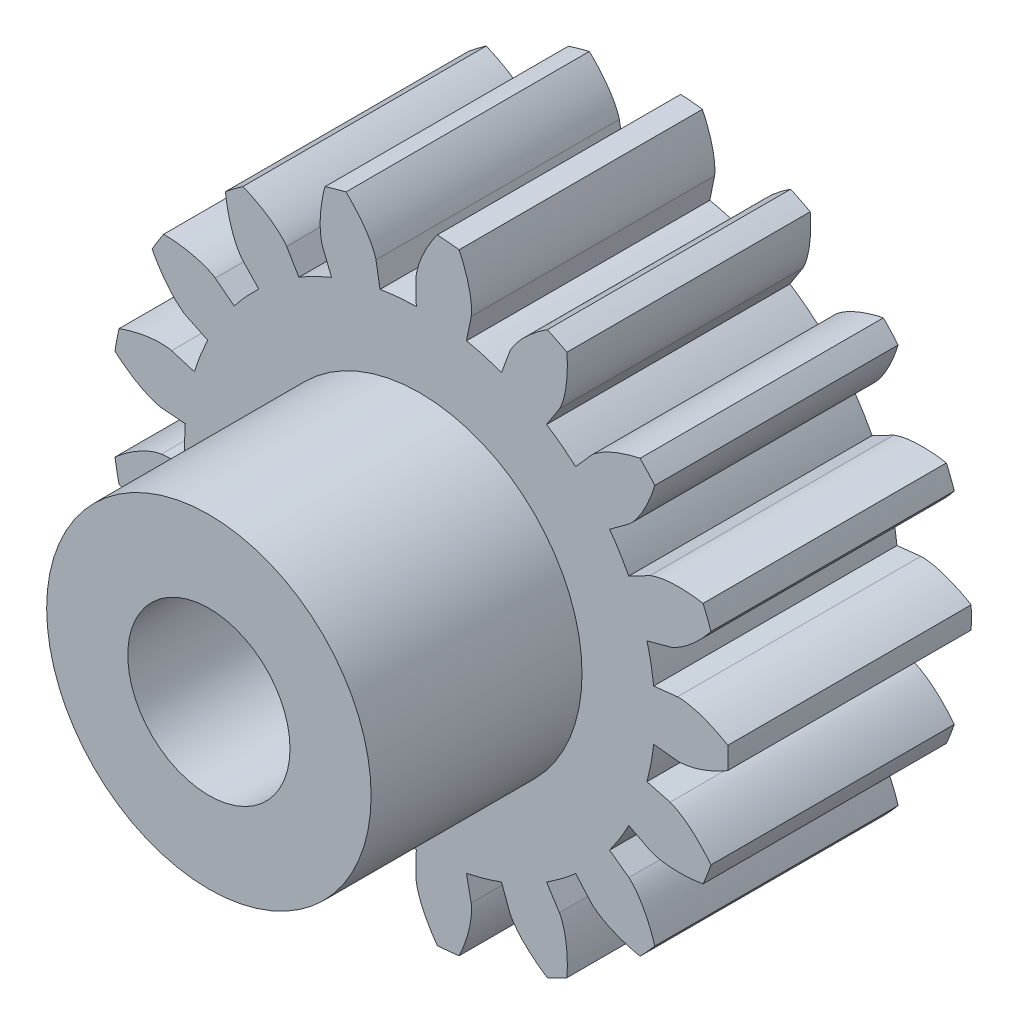
SolidWorks part; units mm, degrees
other "Kamera1"
ref_plane "Płaszczyzna przednia" through (0, 0, 0) normal (0, 0, 1) x (1, 0, 0)
ref_plane "Płaszczyzna górna" through (0, 0, 0) normal (0, 1, 0) x (1, 0, 0)
ref_plane "Płaszczyzna prawa" through (0, 0, 0) normal (1, 0, 0) x (0, 0, -1)
sketch "Szkic1" plane through (0, 0, 0) normal (0, 0, 1) x (1, 0, 0)
  circle A0 centre (0, 0) radius 9.5
extrude "Dodanie-wyciągnięcie1" add sketch "Szkic1" along normal blind 7.5
sketch "Szkic2" plane through (0, 0, 7.5) normal (0, 0, 1) x (1, 0, 0)
  circle A0 centre (0, 0) radius 5
extrude "Dodanie-wyciągnięcie2" add sketch "Szkic2" along normal blind 6.5
sketch "Szkic3" plane through (0, 0, 14) normal (0, 0, 1) x (1, 0, 0)
  circle A0 centre (0, 0) radius 2.5
extrude "Wytnij-wyciągnięcie1" cut sketch "Szkic3" against normal through all
sketch "Szkic5" plane through (0, 0, 0) normal (0, 0, -1) x (-1, 0, 0)
  line L0 (7.9634, 0.6184) -> (7.2282, 0.5613)
  line L1 (7.2282, -0.5613) -> (7.9634, -0.6184)
  line L2 (7.649, -2.3001) -> (6.9429, -2.0878)
  line L3 (6.5374, -3.1345) -> (7.2023, -3.4533)
  line L4 (6.3016, -4.9079) -> (5.7199, -4.4548)
  line L5 (4.9636, -5.2844) -> (5.4684, -5.8219)
  line L6 (4.1031, -6.8529) -> (3.7243, -6.2203)
  line L7 (2.7195, -6.7206) -> (2.9961, -7.4042)
  line L8 (1.3505, -7.8724) -> (1.2258, -7.1456)
  line L9 (0.1081, -7.2492) -> (0.119, -7.9865)
  line L10 (-1.5845, -7.8286) -> (-1.4382, -7.1059)
  line L11 (-2.518, -6.7987) -> (-2.7741, -7.4902)
  line L12 (-4.3056, -6.7276) -> (-3.9081, -6.1065)
  line L13 (-4.8039, -5.43) -> (-5.2925, -5.9823)
  line L14 (-6.4451, -4.7179) -> (-5.8501, -4.2824)
  line L15 (-6.441, -3.328) -> (-7.0962, -3.6665)
  line L16 (-7.7142, -2.0711) -> (-7.002, -1.8799)
  line L17 (-7.2083, -0.7765) -> (-7.9414, -0.8554)
  line L18 (-7.9414, 0.8554) -> (-7.2083, 0.7765)
  line L19 (-7.002, 1.8799) -> (-7.7142, 2.0711)
  line L20 (-7.0962, 3.6665) -> (-6.441, 3.328)
  line L21 (-5.8501, 4.2824) -> (-6.4451, 4.7179)
  line L22 (-5.2925, 5.9823) -> (-4.8039, 5.43)
  line L23 (-3.9081, 6.1065) -> (-4.3056, 6.7276)
  line L24 (-2.7741, 7.4902) -> (-2.518, 6.7987)
  line L25 (-1.4382, 7.1059) -> (-1.5845, 7.8286)
  line L26 (0.119, 7.9865) -> (0.1081, 7.2492)
  line L27 (1.2258, 7.1456) -> (1.3505, 7.8724)
  line L28 (2.9961, 7.4042) -> (2.7195, 6.7206)
  line L29 (3.7243, 6.2203) -> (4.1031, 6.8529)
  line L30 (5.4684, 5.8219) -> (4.9636, 5.2844)
  line L31 (5.7199, 4.4548) -> (6.3016, 4.9079)
  line L32 (7.2023, 3.4533) -> (6.5374, 3.1345)
  line L33 (6.9429, 2.0878) -> (7.649, 2.3001)
  circle A1 centre (0, 0) radius 9.5
  spline S0 degree 4 poles (7.9634, -0.6184) (7.9667, -0.6187) (7.976, -0.6197) (7.9934, -0.6223) (8.0218, -0.6274) (8.0577, -0.6353) (8.1038, -0.647) (8.1577, -0.6627) (8.2166, -0.682) (8.2801, -0.7052) (8.3429, -0.7302) (8.405, -0.757) (8.4665, -0.7852) (8.5402, -0.8212) (8.6279, -0.867) (8.7289, -0.9243) (8.8418, -0.9935) (8.9549, -1.0687) (9.0646, -1.1464) (9.1734, -1.2291) (9.2772, -1.3122) (9.3829, -1.4026) (9.4793, -1.4883) (9.5847, -1.5888) (9.669, -1.6713) (9.7774, -1.7849) (9.8406, -1.8533) (9.9135, -1.9351) (9.9453, -1.9723) (9.9649, -1.9951) knots 0 0 0 0 0 0.005377 0.015084 0.028532 0.04661 0.064855 0.092111 0.119476 0.146842 0.174209 0.201575 0.228941 0.256307 0.307035 0.361767 0.4165 0.471232 0.525964 0.580697 0.635429 0.690161 0.744894 0.799626 0.854358 0.909091 0.954545 1 1 1 1 1 construction
  spline S1 degree 4 poles (7.9634, -0.6184) (7.9667, -0.6187) (7.976, -0.6197) (7.9934, -0.6223) (8.0218, -0.6274) (8.0577, -0.6353) (8.1038, -0.647) (8.1577, -0.6627) (8.2166, -0.682) (8.2801, -0.7052) (8.3429, -0.7302) (8.405, -0.757) (8.4665, -0.7852) (8.5402, -0.8212) (8.6279, -0.867) (8.7289, -0.9243) (8.8418, -0.9935) (8.9549, -1.0687) (9.0646, -1.1464) (9.1734, -1.2291) (9.2772, -1.3122) (9.3829, -1.4026) (9.4793, -1.4883) (9.5847, -1.5888) (9.669, -1.6713) (9.7539, -1.7602) (9.7949, -1.8041) (9.8157, -1.8267) knots 0 0 0 0 0 0.005377 0.015084 0.028532 0.04661 0.064855 0.092111 0.119476 0.146842 0.174209 0.201575 0.228941 0.256307 0.307035 0.361767 0.4165 0.471232 0.525964 0.580697 0.635429 0.690161 0.744894 0.799626 0.854358 0.909091 0.909091 0.909091 0.909091 0.909091
  spline S2 degree 4 poles (7.9634, 0.6184) (7.9667, 0.6187) (7.976, 0.6197) (7.9934, 0.6223) (8.0218, 0.6274) (8.0577, 0.6353) (8.1038, 0.647) (8.1577, 0.6627) (8.2166, 0.682) (8.2801, 0.7052) (8.3429, 0.7302) (8.405, 0.757) (8.4665, 0.7852) (8.5402, 0.8212) (8.6279, 0.867) (8.7289, 0.9243) (8.8418, 0.9935) (8.9549, 1.0687) (9.0646, 1.1464) (9.1734, 1.2291) (9.2772, 1.3122) (9.3829, 1.4026) (9.4793, 1.4883) (9.5847, 1.5888) (9.669, 1.6713) (9.7774, 1.7849) (9.8406, 1.8533) (9.9135, 1.9351) (9.9453, 1.9723) (9.9649, 1.9951) knots 0 0 0 0 0 0.005377 0.015084 0.028532 0.04661 0.064855 0.092111 0.119476 0.146842 0.174209 0.201575 0.228941 0.256307 0.307035 0.361767 0.4165 0.471232 0.525964 0.580697 0.635429 0.690161 0.744894 0.799626 0.854358 0.909091 0.954545 1 1 1 1 1 construction
  spline S3 degree 4 poles (7.9634, 0.6184) (7.9667, 0.6187) (7.976, 0.6197) (7.9934, 0.6223) (8.0218, 0.6274) (8.0577, 0.6353) (8.1038, 0.647) (8.1577, 0.6627) (8.2166, 0.682) (8.2801, 0.7052) (8.3429, 0.7302) (8.405, 0.757) (8.4665, 0.7852) (8.5402, 0.8212) (8.6279, 0.867) (8.7289, 0.9243) (8.8418, 0.9935) (8.9549, 1.0687) (9.0646, 1.1464) (9.1734, 1.2291) (9.2772, 1.3122) (9.3829, 1.4026) (9.4793, 1.4883) (9.5847, 1.5888) (9.669, 1.6713) (9.7539, 1.7602) (9.7949, 1.8041) (9.8157, 1.8267) knots 0 0 0 0 0 0.005377 0.015084 0.028532 0.04661 0.064855 0.092111 0.119476 0.146842 0.174209 0.201575 0.228941 0.256307 0.307035 0.361767 0.4165 0.471232 0.525964 0.580697 0.635429 0.690161 0.744894 0.799626 0.854358 0.909091 0.909091 0.909091 0.909091 0.909091
  spline S4 degree 2 poles (7.2282, 0.5613) (7.2716, -0.0034) (7.2282, -0.5613) knots 0 0 0 0.499734 0.499734 0.499734
  spline S5 degree 2 poles (6.9429, -2.0878) (6.7793, -2.6299) (6.5374, -3.1345) knots 0 0 0 0.499734 0.499734 0.499734
  spline S6 degree 4 poles (7.2023, -3.4533) (7.2053, -3.4548) (7.2135, -3.4591) (7.2288, -3.4678) (7.2534, -3.4829) (7.284, -3.5032) (7.3228, -3.5307) (7.3675, -3.5649) (7.4154, -3.6041) (7.4662, -3.6487) (7.5157, -3.6947) (7.564, -3.7421) (7.6111, -3.7906) (7.6669, -3.8509) (7.732, -3.9252) (7.8056, -4.0151) (7.8858, -4.1205) (7.9641, -4.2314) (8.0383, -4.3435) (8.1099, -4.4599) (8.1767, -4.5749) (8.2426, -4.6974) (8.3015, -4.8121) (8.3635, -4.9439) (8.4124, -5.0513) (8.4724, -5.1963) (8.5066, -5.283) (8.545, -5.3856) (8.5612, -5.4317) (8.5713, -5.4601) knots 0 0 0 0 0 0.005377 0.015084 0.028532 0.04661 0.064855 0.092111 0.119476 0.146842 0.174209 0.201575 0.228941 0.256307 0.307035 0.361767 0.4165 0.471232 0.525964 0.580697 0.635429 0.690161 0.744894 0.799626 0.854358 0.909091 0.954545 1 1 1 1 1 construction
  spline S7 degree 4 poles (7.2023, -3.4533) (7.2053, -3.4548) (7.2135, -3.4591) (7.2288, -3.4678) (7.2534, -3.4829) (7.284, -3.5032) (7.3228, -3.5307) (7.3675, -3.5649) (7.4154, -3.6041) (7.4662, -3.6487) (7.5157, -3.6947) (7.564, -3.7421) (7.6111, -3.7906) (7.6669, -3.8509) (7.732, -3.9252) (7.8056, -4.0151) (7.8858, -4.1205) (7.9641, -4.2314) (8.0383, -4.3435) (8.1099, -4.4599) (8.1767, -4.5749) (8.2426, -4.6974) (8.3015, -4.8121) (8.3635, -4.9439) (8.4124, -5.0513) (8.4594, -5.1649) (8.4818, -5.2206) (8.493, -5.2492) knots 0 0 0 0 0 0.005377 0.015084 0.028532 0.04661 0.064855 0.092111 0.119476 0.146842 0.174209 0.201575 0.228941 0.256307 0.307035 0.361767 0.4165 0.471232 0.525964 0.580697 0.635429 0.690161 0.744894 0.799626 0.854358 0.909091 0.909091 0.909091 0.909091 0.909091
  spline S8 degree 4 poles (7.649, -2.3001) (7.6522, -2.301) (7.6612, -2.3034) (7.6784, -2.3073) (7.7067, -2.3127) (7.743, -2.3184) (7.7903, -2.3241) (7.8463, -2.329) (7.9081, -2.3322) (7.9757, -2.3335) (8.0433, -2.3329) (8.1109, -2.3304) (8.1784, -2.3263) (8.2602, -2.3193) (8.3584, -2.3083) (8.4733, -2.2914) (8.6036, -2.2676) (8.7363, -2.2383) (8.8666, -2.2055) (8.9979, -2.1677) (9.1247, -2.1278) (9.2559, -2.0816) (9.3768, -2.0365) (9.5114, -1.9809) (9.6198, -1.9344) (9.7619, -1.8677) (9.8456, -1.8266) (9.9431, -1.7767) (9.9862, -1.7536) (10.0127, -1.7393) knots 0 0 0 0 0 0.005377 0.015084 0.028532 0.04661 0.064855 0.092111 0.119476 0.146842 0.174209 0.201575 0.228941 0.256307 0.307035 0.361767 0.4165 0.471232 0.525964 0.580697 0.635429 0.690161 0.744894 0.799626 0.854358 0.909091 0.954545 1 1 1 1 1 construction
  spline S9 degree 4 poles (7.649, -2.3001) (7.6522, -2.301) (7.6612, -2.3034) (7.6784, -2.3073) (7.7067, -2.3127) (7.743, -2.3184) (7.7903, -2.3241) (7.8463, -2.329) (7.9081, -2.3322) (7.9757, -2.3335) (8.0433, -2.3329) (8.1109, -2.3304) (8.1784, -2.3263) (8.2602, -2.3193) (8.3584, -2.3083) (8.4733, -2.2914) (8.6036, -2.2676) (8.7363, -2.2383) (8.8666, -2.2055) (8.9979, -2.1677) (9.1247, -2.1278) (9.2559, -2.0816) (9.3768, -2.0365) (9.5114, -1.9809) (9.6198, -1.9344) (9.7311, -1.8822) (9.7852, -1.8561) (9.8128, -1.8425) knots 0 0 0 0 0 0.005377 0.015084 0.028532 0.04661 0.064855 0.092111 0.119476 0.146842 0.174209 0.201575 0.228941 0.256307 0.307035 0.361767 0.4165 0.471232 0.525964 0.580697 0.635429 0.690161 0.744894 0.799626 0.854358 0.909091 0.909091 0.909091 0.909091 0.909091
  spline S10 degree 2 poles (5.7199, -4.4548) (5.3715, -4.9013) (4.9636, -5.2844) knots 0 0 0 0.499734 0.499734 0.499734
  spline S11 degree 4 poles (5.4684, -5.8219) (5.4707, -5.8244) (5.4768, -5.8314) (5.488, -5.845) (5.5055, -5.8679) (5.5267, -5.8979) (5.5529, -5.9376) (5.5822, -5.9856) (5.6127, -6.0395) (5.644, -6.0994) (5.6735, -6.1602) (5.7014, -6.2218) (5.7278, -6.2841) (5.7581, -6.3604) (5.7919, -6.4533) (5.828, -6.5637) (5.8648, -6.6909) (5.8978, -6.8227) (5.9265, -6.954) (5.9511, -7.0884) (5.9719, -7.2197) (5.9891, -7.3577) (6.0026, -7.486) (6.0128, -7.6313) (6.0196, -7.7491) (6.0232, -7.906) (6.0237, -7.9992) (6.0225, -8.1087) (6.0209, -8.1576) (6.02, -8.1877) knots 0 0 0 0 0 0.005377 0.015084 0.028532 0.04661 0.064855 0.092111 0.119476 0.146842 0.174209 0.201575 0.228941 0.256307 0.307035 0.361767 0.4165 0.471232 0.525964 0.580697 0.635429 0.690161 0.744894 0.799626 0.854358 0.909091 0.954545 1 1 1 1 1 construction
  spline S12 degree 4 poles (5.4684, -5.8219) (5.4707, -5.8244) (5.4768, -5.8314) (5.488, -5.845) (5.5055, -5.8679) (5.5267, -5.8979) (5.5529, -5.9376) (5.5822, -5.9856) (5.6127, -6.0395) (5.644, -6.0994) (5.6735, -6.1602) (5.7014, -6.2218) (5.7278, -6.2841) (5.7581, -6.3604) (5.7919, -6.4533) (5.828, -6.5637) (5.8648, -6.6909) (5.8978, -6.8227) (5.9265, -6.954) (5.9511, -7.0884) (5.9719, -7.2197) (5.9891, -7.3577) (6.0026, -7.486) (6.0128, -7.6313) (6.0196, -7.7491) (6.0224, -7.872) (6.0231, -7.932) (6.0233, -7.9627) knots 0 0 0 0 0 0.005377 0.015084 0.028532 0.04661 0.064855 0.092111 0.119476 0.146842 0.174209 0.201575 0.228941 0.256307 0.307035 0.361767 0.4165 0.471232 0.525964 0.580697 0.635429 0.690161 0.744894 0.799626 0.854358 0.909091 0.909091 0.909091 0.909091 0.909091
  spline S13 degree 4 poles (6.3016, -4.9079) (6.3043, -4.9099) (6.3118, -4.9154) (6.3265, -4.9253) (6.3509, -4.9405) (6.3827, -4.9589) (6.4247, -4.9814) (6.4751, -5.0061) (6.5316, -5.0315) (6.5941, -5.0571) (6.6574, -5.0809) (6.7214, -5.103) (6.7858, -5.1235) (6.8646, -5.1466) (6.9602, -5.1718) (7.0734, -5.1976) (7.2035, -5.2224) (7.3377, -5.2431) (7.4711, -5.2596) (7.6073, -5.2717) (7.7399, -5.2803) (7.879, -5.2846) (8.0079, -5.2863) (8.1536, -5.283) (8.2714, -5.2789) (8.428, -5.268) (8.5209, -5.2599) (8.6298, -5.2486) (8.6783, -5.2426) (8.7082, -5.2389) knots 0 0 0 0 0 0.005377 0.015084 0.028532 0.04661 0.064855 0.092111 0.119476 0.146842 0.174209 0.201575 0.228941 0.256307 0.307035 0.361767 0.4165 0.471232 0.525964 0.580697 0.635429 0.690161 0.744894 0.799626 0.854358 0.909091 0.954545 1 1 1 1 1 construction
  spline S14 degree 4 poles (6.3016, -4.9079) (6.3043, -4.9099) (6.3118, -4.9154) (6.3265, -4.9253) (6.3509, -4.9405) (6.3827, -4.9589) (6.4247, -4.9814) (6.4751, -5.0061) (6.5316, -5.0315) (6.5941, -5.0571) (6.6574, -5.0809) (6.7214, -5.103) (6.7858, -5.1235) (6.8646, -5.1466) (6.9602, -5.1718) (7.0734, -5.1976) (7.2035, -5.2224) (7.3377, -5.2431) (7.4711, -5.2596) (7.6073, -5.2717) (7.7399, -5.2803) (7.879, -5.2846) (8.0079, -5.2863) (8.1536, -5.283) (8.2714, -5.2789) (8.3941, -5.2704) (8.4539, -5.2656) (8.4845, -5.2629) knots 0 0 0 0 0 0.005377 0.015084 0.028532 0.04661 0.064855 0.092111 0.119476 0.146842 0.174209 0.201575 0.228941 0.256307 0.307035 0.361767 0.4165 0.471232 0.525964 0.580697 0.635429 0.690161 0.744894 0.799626 0.854358 0.909091 0.909091 0.909091 0.909091 0.909091
  spline S15 degree 2 poles (3.7243, -6.2203) (3.2382, -6.5107) (2.7195, -6.7206) knots 0 0 0 0.499734 0.499734 0.499734
  spline S16 degree 4 poles (2.9961, -7.4042) (2.9973, -7.4073) (3.0005, -7.416) (3.0059, -7.4328) (3.014, -7.4605) (3.0229, -7.4961) (3.033, -7.5426) (3.043, -7.5979) (3.0519, -7.6592) (3.0595, -7.7263) (3.0651, -7.7937) (3.0688, -7.8613) (3.0709, -7.9288) (3.0716, -8.011) (3.0696, -8.1098) (3.0634, -8.2258) (3.0517, -8.3577) (3.0349, -8.4925) (3.0142, -8.6253) (2.9886, -8.7595) (2.9606, -8.8895) (2.9267, -9.0244) (2.893, -9.1489) (2.85, -9.2881) (2.8138, -9.4003) (2.7604, -9.548) (2.7273, -9.635) (2.6866, -9.7367) (2.6675, -9.7818) (2.6558, -9.8095) knots 0 0 0 0 0 0.005377 0.015084 0.028532 0.04661 0.064855 0.092111 0.119476 0.146842 0.174209 0.201575 0.228941 0.256307 0.307035 0.361767 0.4165 0.471232 0.525964 0.580697 0.635429 0.690161 0.744894 0.799626 0.854358 0.909091 0.954545 1 1 1 1 1 construction
  spline S17 degree 4 poles (2.9961, -7.4042) (2.9973, -7.4073) (3.0005, -7.416) (3.0059, -7.4328) (3.014, -7.4605) (3.0229, -7.4961) (3.033, -7.5426) (3.043, -7.5979) (3.0519, -7.6592) (3.0595, -7.7263) (3.0651, -7.7937) (3.0688, -7.8613) (3.0709, -7.9288) (3.0716, -8.011) (3.0696, -8.1098) (3.0634, -8.2258) (3.0517, -8.3577) (3.0349, -8.4925) (3.0142, -8.6253) (2.9886, -8.7595) (2.9606, -8.8895) (2.9267, -9.0244) (2.893, -9.1489) (2.85, -9.2881) (2.8138, -9.4003) (2.772, -9.516) (2.751, -9.5722) (2.74, -9.6009) knots 0 0 0 0 0 0.005377 0.015084 0.028532 0.04661 0.064855 0.092111 0.119476 0.146842 0.174209 0.201575 0.228941 0.256307 0.307035 0.361767 0.4165 0.471232 0.525964 0.580697 0.635429 0.690161 0.744894 0.799626 0.854358 0.909091 0.909091 0.909091 0.909091 0.909091
  spline S18 degree 4 poles (4.1031, -6.8529) (4.1049, -6.8557) (4.1099, -6.8636) (4.12, -6.878) (4.1373, -6.9011) (4.1603, -6.9297) (4.1913, -6.9658) (4.2295, -7.0071) (4.273, -7.0512) (4.322, -7.0977) (4.3724, -7.1427) (4.4241, -7.1865) (4.4767, -7.2289) (4.5419, -7.2789) (4.6219, -7.3369) (4.7182, -7.4018) (4.8305, -7.472) (4.9482, -7.5397) (5.0666, -7.6033) (5.1892, -7.6638) (5.3098, -7.7197) (5.4379, -7.774) (5.5575, -7.8221) (5.6945, -7.8717) (5.8059, -7.9104) (5.9559, -7.9568) (6.0454, -7.9828) (6.151, -8.0116) (6.1985, -8.0235) (6.2277, -8.0309) knots 0 0 0 0 0 0.005377 0.015084 0.028532 0.04661 0.064855 0.092111 0.119476 0.146842 0.174209 0.201575 0.228941 0.256307 0.307035 0.361767 0.4165 0.471232 0.525964 0.580697 0.635429 0.690161 0.744894 0.799626 0.854358 0.909091 0.954545 1 1 1 1 1 construction
  spline S19 degree 4 poles (4.1031, -6.8529) (4.1049, -6.8557) (4.1099, -6.8636) (4.12, -6.878) (4.1373, -6.9011) (4.1603, -6.9297) (4.1913, -6.9658) (4.2295, -7.0071) (4.273, -7.0512) (4.322, -7.0977) (4.3724, -7.1427) (4.4241, -7.1865) (4.4767, -7.2289) (4.5419, -7.2789) (4.6219, -7.3369) (4.7182, -7.4018) (4.8305, -7.472) (4.9482, -7.5397) (5.0666, -7.6033) (5.1892, -7.6638) (5.3098, -7.7197) (5.4379, -7.774) (5.5575, -7.8221) (5.6945, -7.8717) (5.8059, -7.9104) (5.9234, -7.9468) (5.9809, -7.9639) (6.0104, -7.9724) knots 0 0 0 0 0 0.005377 0.015084 0.028532 0.04661 0.064855 0.092111 0.119476 0.146842 0.174209 0.201575 0.228941 0.256307 0.307035 0.361767 0.4165 0.471232 0.525964 0.580697 0.635429 0.690161 0.744894 0.799626 0.854358 0.909091 0.909091 0.909091 0.909091 0.909091
  spline S20 degree 2 poles (1.2258, -7.1456) (0.6676, -7.2409) (0.1081, -7.2492) knots 0 0 0 0.499734 0.499734 0.499734
  spline S21 degree 4 poles (0.119, -7.9865) (0.119, -7.9898) (0.1189, -7.9991) (0.1179, -8.0167) (0.1154, -8.0454) (0.1109, -8.0819) (0.1035, -8.1289) (0.0928, -8.1841) (0.079, -8.2445) (0.0618, -8.3098) (0.0427, -8.3747) (0.0218, -8.439) (-0.0007, -8.5028) (-0.0297, -8.5796) (-0.0673, -8.671) (-0.1149, -8.7769) (-0.1735, -8.8957) (-0.2379, -9.0153) (-0.3051, -9.1317) (-0.3775, -9.2476) (-0.4506, -9.3587) (-0.5309, -9.4722) (-0.6073, -9.5761) (-0.6977, -9.6904) (-0.772, -9.782) (-0.8751, -9.9004) (-0.9375, -9.9696) (-1.0121, -10.0497) (-1.0462, -10.0848) (-1.0672, -10.1065) knots 0 0 0 0 0 0.005377 0.015084 0.028532 0.04661 0.064855 0.092111 0.119476 0.146842 0.174209 0.201575 0.228941 0.256307 0.307035 0.361767 0.4165 0.471232 0.525964 0.580697 0.635429 0.690161 0.744894 0.799626 0.854358 0.909091 0.954545 1 1 1 1 1 construction
  spline S22 degree 4 poles (0.119, -7.9865) (0.119, -7.9898) (0.1189, -7.9991) (0.1179, -8.0167) (0.1154, -8.0454) (0.1109, -8.0819) (0.1035, -8.1289) (0.0928, -8.1841) (0.079, -8.2445) (0.0618, -8.3098) (0.0427, -8.3747) (0.0218, -8.439) (-0.0007, -8.5028) (-0.0297, -8.5796) (-0.0673, -8.671) (-0.1149, -8.7769) (-0.1735, -8.8957) (-0.2379, -9.0153) (-0.3051, -9.1317) (-0.3775, -9.2476) (-0.4506, -9.3587) (-0.5309, -9.4722) (-0.6073, -9.5761) (-0.6977, -9.6904) (-0.772, -9.782) (-0.8527, -9.8747) (-0.8926, -9.9196) (-0.9132, -9.9424) knots 0 0 0 0 0 0.005377 0.015084 0.028532 0.04661 0.064855 0.092111 0.119476 0.146842 0.174209 0.201575 0.228941 0.256307 0.307035 0.361767 0.4165 0.471232 0.525964 0.580697 0.635429 0.690161 0.744894 0.799626 0.854358 0.909091 0.909091 0.909091 0.909091 0.909091
  spline S23 degree 4 poles (1.3505, -7.8724) (1.3511, -7.8757) (1.353, -7.8848) (1.3572, -7.9019) (1.3649, -7.9296) (1.3761, -7.9647) (1.392, -8.0095) (1.4126, -8.0618) (1.4372, -8.1186) (1.4662, -8.1797) (1.4969, -8.2399) (1.5293, -8.2993) (1.563, -8.3579) (1.6057, -8.428) (1.6594, -8.511) (1.7257, -8.6064) (1.8051, -8.7124) (1.8904, -8.8181) (1.9779, -8.9201) (2.0703, -9.0208) (2.1626, -9.1166) (2.2624, -9.2134) (2.3566, -9.3015) (2.4664, -9.3972) (2.5563, -9.4736) (2.6794, -9.571) (2.7534, -9.6276) (2.8415, -9.6926) (2.8815, -9.7209) (2.906, -9.7383) knots 0 0 0 0 0 0.005377 0.015084 0.028532 0.04661 0.064855 0.092111 0.119476 0.146842 0.174209 0.201575 0.228941 0.256307 0.307035 0.361767 0.4165 0.471232 0.525964 0.580697 0.635429 0.690161 0.744894 0.799626 0.854358 0.909091 0.954545 1 1 1 1 1 construction
  spline S24 degree 4 poles (1.3505, -7.8724) (1.3511, -7.8757) (1.353, -7.8848) (1.3572, -7.9019) (1.3649, -7.9296) (1.3761, -7.9647) (1.392, -8.0095) (1.4126, -8.0618) (1.4372, -8.1186) (1.4662, -8.1797) (1.4969, -8.2399) (1.5293, -8.2993) (1.563, -8.3579) (1.6057, -8.428) (1.6594, -8.511) (1.7257, -8.6064) (1.8051, -8.7124) (1.8904, -8.8181) (1.9779, -8.9201) (2.0703, -9.0208) (2.1626, -9.1166) (2.2624, -9.2134) (2.3566, -9.3015) (2.4664, -9.3972) (2.5563, -9.4736) (2.6527, -9.5499) (2.7001, -9.5867) (2.7246, -9.6053) knots 0 0 0 0 0 0.005377 0.015084 0.028532 0.04661 0.064855 0.092111 0.119476 0.146842 0.174209 0.201575 0.228941 0.256307 0.307035 0.361767 0.4165 0.471232 0.525964 0.580697 0.635429 0.690161 0.744894 0.799626 0.854358 0.909091 0.909091 0.909091 0.909091 0.909091
  spline S25 degree 2 poles (-1.4382, -7.1059) (-1.9932, -6.9931) (-2.518, -6.7987) knots 0 0 0 0.499734 0.499734 0.499734
  spline S26 degree 4 poles (-2.7741, -7.4902) (-2.7753, -7.4933) (-2.7788, -7.5019) (-2.786, -7.518) (-2.7987, -7.5438) (-2.8161, -7.5762) (-2.84, -7.6174) (-2.8699, -7.665) (-2.9046, -7.7163) (-2.9442, -7.771) (-2.9855, -7.8246) (-3.0282, -7.877) (-3.0722, -7.9284) (-3.127, -7.9895) (-3.1951, -8.0612) (-3.2778, -8.1427) (-3.3753, -8.2324) (-3.4785, -8.3206) (-3.5833, -8.4048) (-3.6926, -8.4868) (-3.8009, -8.564) (-3.9168, -8.6408) (-4.0256, -8.7101) (-4.1511, -8.784) (-4.2536, -8.8426) (-4.3924, -8.9157) (-4.4756, -8.9577) (-4.5742, -9.0054) (-4.6186, -9.0259) (-4.646, -9.0385) knots 0 0 0 0 0 0.005377 0.015084 0.028532 0.04661 0.064855 0.092111 0.119476 0.146842 0.174209 0.201575 0.228941 0.256307 0.307035 0.361767 0.4165 0.471232 0.525964 0.580697 0.635429 0.690161 0.744894 0.799626 0.854358 0.909091 0.954545 1 1 1 1 1 construction
  spline S27 degree 4 poles (-2.7741, -7.4902) (-2.7753, -7.4933) (-2.7788, -7.5019) (-2.786, -7.518) (-2.7987, -7.5438) (-2.8161, -7.5762) (-2.84, -7.6174) (-2.8699, -7.665) (-2.9046, -7.7163) (-2.9442, -7.771) (-2.9855, -7.8246) (-3.0282, -7.877) (-3.0722, -7.9284) (-3.127, -7.9895) (-3.1951, -8.0612) (-3.2778, -8.1427) (-3.3753, -8.2324) (-3.4785, -8.3206) (-3.5833, -8.4048) (-3.6926, -8.4868) (-3.8009, -8.564) (-3.9168, -8.6408) (-4.0256, -8.7101) (-4.1511, -8.784) (-4.2536, -8.8426) (-4.3623, -8.8999) (-4.4157, -8.9273) (-4.4432, -8.9411) knots 0 0 0 0 0 0.005377 0.015084 0.028532 0.04661 0.064855 0.092111 0.119476 0.146842 0.174209 0.201575 0.228941 0.256307 0.307035 0.361767 0.4165 0.471232 0.525964 0.580697 0.635429 0.690161 0.744894 0.799626 0.854358 0.909091 0.909091 0.909091 0.909091 0.909091
  spline S28 degree 4 poles (-1.5845, -7.8286) (-1.5851, -7.8319) (-1.5867, -7.8411) (-1.589, -7.8586) (-1.5918, -7.8872) (-1.594, -7.9239) (-1.5954, -7.9715) (-1.5951, -8.0277) (-1.5926, -8.0896) (-1.5877, -8.157) (-1.5808, -8.2242) (-1.5721, -8.2913) (-1.5617, -8.3581) (-1.5473, -8.439) (-1.5272, -8.5358) (-1.4998, -8.6486) (-1.4641, -8.7761) (-1.4227, -8.9055) (-1.378, -9.0323) (-1.3282, -9.1595) (-1.2768, -9.2821) (-1.2187, -9.4085) (-1.1627, -9.5247) (-1.0948, -9.6536) (-1.0386, -9.7573) (-0.959, -9.8926) (-0.9104, -9.9721) (-0.8517, -10.0646) (-0.8247, -10.1054) (-0.8081, -10.1305) knots 0 0 0 0 0 0.005377 0.015084 0.028532 0.04661 0.064855 0.092111 0.119476 0.146842 0.174209 0.201575 0.228941 0.256307 0.307035 0.361767 0.4165 0.471232 0.525964 0.580697 0.635429 0.690161 0.744894 0.799626 0.854358 0.909091 0.954545 1 1 1 1 1 construction
  spline S29 degree 4 poles (-1.5845, -7.8286) (-1.5851, -7.8319) (-1.5867, -7.8411) (-1.589, -7.8586) (-1.5918, -7.8872) (-1.594, -7.9239) (-1.5954, -7.9715) (-1.5951, -8.0277) (-1.5926, -8.0896) (-1.5877, -8.157) (-1.5808, -8.2242) (-1.5721, -8.2913) (-1.5617, -8.3581) (-1.5473, -8.439) (-1.5272, -8.5358) (-1.4998, -8.6486) (-1.4641, -8.7761) (-1.4227, -8.9055) (-1.378, -9.0323) (-1.3282, -9.1595) (-1.2768, -9.2821) (-1.2187, -9.4085) (-1.1627, -9.5247) (-1.0948, -9.6536) (-1.0386, -9.7573) (-0.9763, -9.8633) (-0.9453, -9.9147) (-0.9292, -9.9409) knots 0 0 0 0 0 0.005377 0.015084 0.028532 0.04661 0.064855 0.092111 0.119476 0.146842 0.174209 0.201575 0.228941 0.256307 0.307035 0.361767 0.4165 0.471232 0.525964 0.580697 0.635429 0.690161 0.744894 0.799626 0.854358 0.909091 0.909091 0.909091 0.909091 0.909091
  spline S30 degree 2 poles (-3.9081, -6.1065) (-4.3848, -5.8008) (-4.8039, -5.43) knots 0 0 0 0.499734 0.499734 0.499734
  spline S31 degree 4 poles (-5.2925, -5.9823) (-5.2947, -5.9847) (-5.3011, -5.9915) (-5.3137, -6.0039) (-5.3349, -6.0234) (-5.3628, -6.0473) (-5.3999, -6.0771) (-5.445, -6.1106) (-5.4959, -6.146) (-5.5526, -6.1827) (-5.6104, -6.2177) (-5.6692, -6.2512) (-5.7288, -6.2832) (-5.802, -6.3204) (-5.8914, -6.3627) (-5.9979, -6.4088) (-6.1212, -6.4572) (-6.2494, -6.5021) (-6.3775, -6.5428) (-6.5091, -6.5798) (-6.6379, -6.6126) (-6.7738, -6.6424) (-6.9002, -6.6677) (-7.044, -6.6913) (-7.1606, -6.7089) (-7.3166, -6.7269) (-7.4093, -6.7361) (-7.5184, -6.7449) (-7.5673, -6.7479) (-7.5973, -6.7498) knots 0 0 0 0 0 0.005377 0.015084 0.028532 0.04661 0.064855 0.092111 0.119476 0.146842 0.174209 0.201575 0.228941 0.256307 0.307035 0.361767 0.4165 0.471232 0.525964 0.580697 0.635429 0.690161 0.744894 0.799626 0.854358 0.909091 0.954545 1 1 1 1 1 construction
  spline S32 degree 4 poles (-5.2925, -5.9823) (-5.2947, -5.9847) (-5.3011, -5.9915) (-5.3137, -6.0039) (-5.3349, -6.0234) (-5.3628, -6.0473) (-5.3999, -6.0771) (-5.445, -6.1106) (-5.4959, -6.146) (-5.5526, -6.1827) (-5.6104, -6.2177) (-5.6692, -6.2512) (-5.7288, -6.2832) (-5.802, -6.3204) (-5.8914, -6.3627) (-5.9979, -6.4088) (-6.1212, -6.4572) (-6.2494, -6.5021) (-6.3775, -6.5428) (-6.5091, -6.5798) (-6.6379, -6.6126) (-6.7738, -6.6424) (-6.9002, -6.6677) (-7.044, -6.6913) (-7.1606, -6.7089) (-7.2827, -6.723) (-7.3424, -6.7293) (-7.373, -6.7323) knots 0 0 0 0 0 0.005377 0.015084 0.028532 0.04661 0.064855 0.092111 0.119476 0.146842 0.174209 0.201575 0.228941 0.256307 0.307035 0.361767 0.4165 0.471232 0.525964 0.580697 0.635429 0.690161 0.744894 0.799626 0.854358 0.909091 0.909091 0.909091 0.909091 0.909091
  spline S33 degree 4 poles (-4.3056, -6.7276) (-4.3073, -6.7304) (-4.3121, -6.7384) (-4.3205, -6.7539) (-4.3335, -6.7796) (-4.3488, -6.813) (-4.3673, -6.8569) (-4.3873, -6.9094) (-4.4073, -6.968) (-4.4271, -7.0326) (-4.445, -7.0978) (-4.4611, -7.1635) (-4.4756, -7.2296) (-4.4913, -7.3102) (-4.5075, -7.4077) (-4.5227, -7.5228) (-4.5355, -7.6546) (-4.5437, -7.7902) (-4.5478, -7.9245) (-4.5473, -8.0612) (-4.5436, -8.1941) (-4.5351, -8.3329) (-4.5249, -8.4615) (-4.5082, -8.6062) (-4.4932, -8.7232) (-4.4679, -8.8782) (-4.4513, -8.9698) (-4.4299, -9.0773) (-4.4195, -9.125) (-4.413, -9.1545) knots 0 0 0 0 0 0.005377 0.015084 0.028532 0.04661 0.064855 0.092111 0.119476 0.146842 0.174209 0.201575 0.228941 0.256307 0.307035 0.361767 0.4165 0.471232 0.525964 0.580697 0.635429 0.690161 0.744894 0.799626 0.854358 0.909091 0.954545 1 1 1 1 1 construction
  spline S34 degree 4 poles (-4.3056, -6.7276) (-4.3073, -6.7304) (-4.3121, -6.7384) (-4.3205, -6.7539) (-4.3335, -6.7796) (-4.3488, -6.813) (-4.3673, -6.8569) (-4.3873, -6.9094) (-4.4073, -6.968) (-4.4271, -7.0326) (-4.445, -7.0978) (-4.4611, -7.1635) (-4.4756, -7.2296) (-4.4913, -7.3102) (-4.5075, -7.4077) (-4.5227, -7.5228) (-4.5355, -7.6546) (-4.5437, -7.7902) (-4.5478, -7.9245) (-4.5473, -8.0612) (-4.5436, -8.1941) (-4.5351, -8.3329) (-4.5249, -8.4615) (-4.5082, -8.6062) (-4.4932, -8.7232) (-4.4734, -8.8446) (-4.4631, -8.9037) (-4.4576, -8.9339) knots 0 0 0 0 0 0.005377 0.015084 0.028532 0.04661 0.064855 0.092111 0.119476 0.146842 0.174209 0.201575 0.228941 0.256307 0.307035 0.361767 0.4165 0.471232 0.525964 0.580697 0.635429 0.690161 0.744894 0.799626 0.854358 0.909091 0.909091 0.909091 0.909091 0.909091
  spline S35 degree 2 poles (-5.8501, -4.2824) (-6.1842, -3.8251) (-6.441, -3.328) knots 0 0 0 0.499734 0.499734 0.499734
  spline S36 degree 4 poles (-7.0962, -3.6665) (-7.0991, -3.6679) (-7.1076, -3.6719) (-7.1237, -3.6789) (-7.1505, -3.6895) (-7.1852, -3.7017) (-7.2306, -3.716) (-7.2847, -3.731) (-7.3449, -3.7456) (-7.4111, -3.7593) (-7.4777, -3.7711) (-7.5446, -3.7811) (-7.6117, -3.7894) (-7.6934, -3.7976) (-7.792, -3.8048) (-7.908, -3.8093) (-8.0405, -3.8099) (-8.1762, -3.8055) (-8.3104, -3.7972) (-8.4464, -3.7841) (-8.5784, -3.7682) (-8.7158, -3.7469) (-8.8429, -3.7248) (-8.9855, -3.6949) (-9.1006, -3.6691) (-9.2525, -3.6296) (-9.3423, -3.6047) (-9.4473, -3.5735) (-9.4939, -3.5587) (-9.5226, -3.5496) knots 0 0 0 0 0 0.005377 0.015084 0.028532 0.04661 0.064855 0.092111 0.119476 0.146842 0.174209 0.201575 0.228941 0.256307 0.307035 0.361767 0.4165 0.471232 0.525964 0.580697 0.635429 0.690161 0.744894 0.799626 0.854358 0.909091 0.954545 1 1 1 1 1 construction
  spline S37 degree 4 poles (-7.0962, -3.6665) (-7.0991, -3.6679) (-7.1076, -3.6719) (-7.1237, -3.6789) (-7.1505, -3.6895) (-7.1852, -3.7017) (-7.2306, -3.716) (-7.2847, -3.731) (-7.3449, -3.7456) (-7.4111, -3.7593) (-7.4777, -3.7711) (-7.5446, -3.7811) (-7.6117, -3.7894) (-7.6934, -3.7976) (-7.792, -3.8048) (-7.908, -3.8093) (-8.0405, -3.8099) (-8.1762, -3.8055) (-8.3104, -3.7972) (-8.4464, -3.7841) (-8.5784, -3.7682) (-8.7158, -3.7469) (-8.8429, -3.7248) (-8.9855, -3.6949) (-9.1006, -3.6691) (-9.2196, -3.6382) (-9.2775, -3.6225) (-9.3071, -3.6142) knots 0 0 0 0 0 0.005377 0.015084 0.028532 0.04661 0.064855 0.092111 0.119476 0.146842 0.174209 0.201575 0.228941 0.256307 0.307035 0.361767 0.4165 0.471232 0.525964 0.580697 0.635429 0.690161 0.744894 0.799626 0.854358 0.909091 0.909091 0.909091 0.909091 0.909091
  spline S38 degree 4 poles (-6.4451, -4.7179) (-6.4478, -4.7199) (-6.4551, -4.7257) (-6.4685, -4.7371) (-6.4899, -4.7564) (-6.5163, -4.782) (-6.5494, -4.8162) (-6.587, -4.858) (-6.6268, -4.9053) (-6.6686, -4.9585) (-6.7088, -5.0128) (-6.7476, -5.0683) (-6.785, -5.1246) (-6.8287, -5.1941) (-6.8791, -5.2791) (-6.9349, -5.381) (-6.9944, -5.4993) (-7.051, -5.6228) (-7.1033, -5.7466) (-7.1523, -5.8742) (-7.1969, -5.9994) (-7.2391, -6.132) (-7.276, -6.2555) (-7.3127, -6.3965) (-7.341, -6.5111) (-7.3733, -6.6647) (-7.391, -6.7561) (-7.4099, -6.864) (-7.4174, -6.9124) (-7.422, -6.9421) knots 0 0 0 0 0 0.005377 0.015084 0.028532 0.04661 0.064855 0.092111 0.119476 0.146842 0.174209 0.201575 0.228941 0.256307 0.307035 0.361767 0.4165 0.471232 0.525964 0.580697 0.635429 0.690161 0.744894 0.799626 0.854358 0.909091 0.954545 1 1 1 1 1 construction
  spline S39 degree 4 poles (-6.4451, -4.7179) (-6.4478, -4.7199) (-6.4551, -4.7257) (-6.4685, -4.7371) (-6.4899, -4.7564) (-6.5163, -4.782) (-6.5494, -4.8162) (-6.587, -4.858) (-6.6268, -4.9053) (-6.6686, -4.9585) (-6.7088, -5.0128) (-6.7476, -5.0683) (-6.785, -5.1246) (-6.8287, -5.1941) (-6.8791, -5.2791) (-6.9349, -5.381) (-6.9944, -5.4993) (-7.051, -5.6228) (-7.1033, -5.7466) (-7.1523, -5.8742) (-7.1969, -5.9994) (-7.2391, -6.132) (-7.276, -6.2555) (-7.3127, -6.3965) (-7.341, -6.5111) (-7.3663, -6.6314) (-7.3781, -6.6902) (-7.3839, -6.7204) knots 0 0 0 0 0 0.005377 0.015084 0.028532 0.04661 0.064855 0.092111 0.119476 0.146842 0.174209 0.201575 0.228941 0.256307 0.307035 0.361767 0.4165 0.471232 0.525964 0.580697 0.635429 0.690161 0.744894 0.799626 0.854358 0.909091 0.909091 0.909091 0.909091 0.909091
  spline S40 degree 2 poles (-7.002, -1.8799) (-7.1484, -1.3328) (-7.2083, -0.7765) knots 0 0 0 0.499734 0.499734 0.499734
  spline S41 degree 4 poles (-7.9414, -0.8554) (-7.9448, -0.8557) (-7.954, -0.8564) (-7.9717, -0.8571) (-8.0005, -0.8572) (-8.0372, -0.8561) (-8.0847, -0.8531) (-8.1406, -0.8475) (-8.202, -0.8394) (-8.2687, -0.8283) (-8.335, -0.8152) (-8.401, -0.8003) (-8.4666, -0.7839) (-8.5457, -0.762) (-8.6403, -0.7331) (-8.7501, -0.6954) (-8.8738, -0.648) (-8.9988, -0.5949) (-9.1209, -0.5387) (-9.243, -0.4774) (-9.3604, -0.4149) (-9.4808, -0.3454) (-9.5913, -0.2789) (-9.7134, -0.1994) (-9.8115, -0.1338) (-9.9389, -0.0421) (-10.0136, 0.0136) (-10.1002, 0.0806) (-10.1383, 0.1112) (-10.1618, 0.1301) knots 0 0 0 0 0 0.005377 0.015084 0.028532 0.04661 0.064855 0.092111 0.119476 0.146842 0.174209 0.201575 0.228941 0.256307 0.307035 0.361767 0.4165 0.471232 0.525964 0.580697 0.635429 0.690161 0.744894 0.799626 0.854358 0.909091 0.954545 1 1 1 1 1 construction
  spline S42 degree 4 poles (-7.9414, -0.8554) (-7.9448, -0.8557) (-7.954, -0.8564) (-7.9717, -0.8571) (-8.0005, -0.8572) (-8.0372, -0.8561) (-8.0847, -0.8531) (-8.1406, -0.8475) (-8.202, -0.8394) (-8.2687, -0.8283) (-8.335, -0.8152) (-8.401, -0.8003) (-8.4666, -0.7839) (-8.5457, -0.762) (-8.6403, -0.7331) (-8.7501, -0.6954) (-8.8738, -0.648) (-8.9988, -0.5949) (-9.1209, -0.5387) (-9.243, -0.4774) (-9.3604, -0.4149) (-9.4808, -0.3454) (-9.5913, -0.2789) (-9.7134, -0.1994) (-9.8115, -0.1338) (-9.9113, -0.062) (-9.9596, -0.0265) (-9.9842, -0.008) knots 0 0 0 0 0 0.005377 0.015084 0.028532 0.04661 0.064855 0.092111 0.119476 0.146842 0.174209 0.201575 0.228941 0.256307 0.307035 0.361767 0.4165 0.471232 0.525964 0.580697 0.635429 0.690161 0.744894 0.799626 0.854358 0.909091 0.909091 0.909091 0.909091 0.909091
  spline S43 degree 4 poles (-7.7142, -2.0711) (-7.7174, -2.072) (-7.7263, -2.0747) (-7.743, -2.0805) (-7.7699, -2.0907) (-7.8037, -2.1051) (-7.8469, -2.125) (-7.8971, -2.1504) (-7.9514, -2.1802) (-8.0095, -2.2147) (-8.0666, -2.2508) (-8.1228, -2.2885) (-8.178, -2.3275) (-8.2439, -2.3765) (-8.3216, -2.4376) (-8.4104, -2.5125) (-8.5087, -2.6013) (-8.606, -2.696) (-8.6996, -2.7925) (-8.7913, -2.8938) (-8.8781, -2.9945) (-8.9654, -3.1028) (-9.0444, -3.2047) (-9.1296, -3.3229) (-9.1973, -3.4195) (-9.283, -3.5511) (-9.3325, -3.63) (-9.3891, -3.7237) (-9.4135, -3.7661) (-9.4286, -3.7922) knots 0 0 0 0 0 0.005377 0.015084 0.028532 0.04661 0.064855 0.092111 0.119476 0.146842 0.174209 0.201575 0.228941 0.256307 0.307035 0.361767 0.4165 0.471232 0.525964 0.580697 0.635429 0.690161 0.744894 0.799626 0.854358 0.909091 0.954545 1 1 1 1 1 construction
  spline S44 degree 4 poles (-7.7142, -2.0711) (-7.7174, -2.072) (-7.7263, -2.0747) (-7.743, -2.0805) (-7.7699, -2.0907) (-7.8037, -2.1051) (-7.8469, -2.125) (-7.8971, -2.1504) (-7.9514, -2.1802) (-8.0095, -2.2147) (-8.0666, -2.2508) (-8.1228, -2.2885) (-8.178, -2.3275) (-8.2439, -2.3765) (-8.3216, -2.4376) (-8.4104, -2.5125) (-8.5087, -2.6013) (-8.606, -2.696) (-8.6996, -2.7925) (-8.7913, -2.8938) (-8.8781, -2.9945) (-8.9654, -3.1028) (-9.0444, -3.2047) (-9.1296, -3.3229) (-9.1973, -3.4195) (-9.2644, -3.5225) (-9.2966, -3.5732) (-9.3129, -3.5992) knots 0 0 0 0 0 0.005377 0.015084 0.028532 0.04661 0.064855 0.092111 0.119476 0.146842 0.174209 0.201575 0.228941 0.256307 0.307035 0.361767 0.4165 0.471232 0.525964 0.580697 0.635429 0.690161 0.744894 0.799626 0.854358 0.909091 0.909091 0.909091 0.909091 0.909091
  spline S45 degree 2 poles (-7.2083, 0.7765) (-7.1471, 1.3395) (-7.002, 1.8799) knots 0 0 0 0.499734 0.499734 0.499734
  spline S46 degree 4 poles (-7.7142, 2.0711) (-7.7174, 2.072) (-7.7263, 2.0747) (-7.743, 2.0805) (-7.7699, 2.0907) (-7.8037, 2.1051) (-7.8469, 2.125) (-7.8971, 2.1504) (-7.9514, 2.1802) (-8.0095, 2.2147) (-8.0666, 2.2508) (-8.1228, 2.2885) (-8.178, 2.3275) (-8.2439, 2.3765) (-8.3216, 2.4376) (-8.4104, 2.5125) (-8.5087, 2.6013) (-8.606, 2.696) (-8.6996, 2.7925) (-8.7913, 2.8938) (-8.8781, 2.9945) (-8.9654, 3.1028) (-9.0444, 3.2047) (-9.1296, 3.3229) (-9.1973, 3.4195) (-9.283, 3.5511) (-9.3325, 3.63) (-9.3891, 3.7237) (-9.4135, 3.7661) (-9.4286, 3.7922) knots 0 0 0 0 0 0.005377 0.015084 0.028532 0.04661 0.064855 0.092111 0.119476 0.146842 0.174209 0.201575 0.228941 0.256307 0.307035 0.361767 0.4165 0.471232 0.525964 0.580697 0.635429 0.690161 0.744894 0.799626 0.854358 0.909091 0.954545 1 1 1 1 1 construction
  spline S47 degree 4 poles (-7.7142, 2.0711) (-7.7174, 2.072) (-7.7263, 2.0747) (-7.743, 2.0805) (-7.7699, 2.0907) (-7.8037, 2.1051) (-7.8469, 2.125) (-7.8971, 2.1504) (-7.9514, 2.1802) (-8.0095, 2.2147) (-8.0666, 2.2508) (-8.1228, 2.2885) (-8.178, 2.3275) (-8.2439, 2.3765) (-8.3216, 2.4376) (-8.4104, 2.5125) (-8.5087, 2.6013) (-8.606, 2.696) (-8.6996, 2.7925) (-8.7913, 2.8938) (-8.8781, 2.9945) (-8.9654, 3.1028) (-9.0444, 3.2047) (-9.1296, 3.3229) (-9.1973, 3.4195) (-9.2644, 3.5225) (-9.2966, 3.5732) (-9.3129, 3.5992) knots 0 0 0 0 0 0.005377 0.015084 0.028532 0.04661 0.064855 0.092111 0.119476 0.146842 0.174209 0.201575 0.228941 0.256307 0.307035 0.361767 0.4165 0.471232 0.525964 0.580697 0.635429 0.690161 0.744894 0.799626 0.854358 0.909091 0.909091 0.909091 0.909091 0.909091
  spline S48 degree 4 poles (-7.9414, 0.8554) (-7.9448, 0.8557) (-7.954, 0.8564) (-7.9717, 0.8571) (-8.0005, 0.8572) (-8.0372, 0.8561) (-8.0847, 0.8531) (-8.1406, 0.8475) (-8.202, 0.8394) (-8.2687, 0.8283) (-8.335, 0.8152) (-8.401, 0.8003) (-8.4666, 0.7839) (-8.5457, 0.762) (-8.6403, 0.7331) (-8.7501, 0.6954) (-8.8738, 0.648) (-8.9988, 0.5949) (-9.1209, 0.5387) (-9.243, 0.4774) (-9.3604, 0.4149) (-9.4808, 0.3454) (-9.5913, 0.2789) (-9.7134, 0.1994) (-9.8115, 0.1338) (-9.9389, 0.0421) (-10.0136, -0.0136) (-10.1002, -0.0806) (-10.1383, -0.1112) (-10.1618, -0.1301) knots 0 0 0 0 0 0.005377 0.015084 0.028532 0.04661 0.064855 0.092111 0.119476 0.146842 0.174209 0.201575 0.228941 0.256307 0.307035 0.361767 0.4165 0.471232 0.525964 0.580697 0.635429 0.690161 0.744894 0.799626 0.854358 0.909091 0.954545 1 1 1 1 1 construction
  spline S49 degree 4 poles (-7.9414, 0.8554) (-7.9448, 0.8557) (-7.954, 0.8564) (-7.9717, 0.8571) (-8.0005, 0.8572) (-8.0372, 0.8561) (-8.0847, 0.8531) (-8.1406, 0.8475) (-8.202, 0.8394) (-8.2687, 0.8283) (-8.335, 0.8152) (-8.401, 0.8003) (-8.4666, 0.7839) (-8.5457, 0.762) (-8.6403, 0.7331) (-8.7501, 0.6954) (-8.8738, 0.648) (-8.9988, 0.5949) (-9.1209, 0.5387) (-9.243, 0.4774) (-9.3604, 0.4149) (-9.4808, 0.3454) (-9.5913, 0.2789) (-9.7134, 0.1994) (-9.8115, 0.1338) (-9.9113, 0.062) (-9.9596, 0.0265) (-9.9842, 0.008) knots 0 0 0 0 0 0.005377 0.015084 0.028532 0.04661 0.064855 0.092111 0.119476 0.146842 0.174209 0.201575 0.228941 0.256307 0.307035 0.361767 0.4165 0.471232 0.525964 0.580697 0.635429 0.690161 0.744894 0.799626 0.854358 0.909091 0.909091 0.909091 0.909091 0.909091
  spline S50 degree 2 poles (-6.441, 3.328) (-6.1806, 3.8308) (-5.8501, 4.2824) knots 0 0 0 0.499734 0.499734 0.499734
  spline S51 degree 4 poles (-6.4451, 4.7179) (-6.4478, 4.7199) (-6.4551, 4.7257) (-6.4685, 4.7371) (-6.4899, 4.7564) (-6.5163, 4.782) (-6.5494, 4.8162) (-6.587, 4.858) (-6.6268, 4.9053) (-6.6686, 4.9585) (-6.7088, 5.0128) (-6.7476, 5.0683) (-6.785, 5.1246) (-6.8287, 5.1941) (-6.8791, 5.2791) (-6.9349, 5.381) (-6.9944, 5.4993) (-7.051, 5.6228) (-7.1033, 5.7466) (-7.1523, 5.8742) (-7.1969, 5.9994) (-7.2391, 6.132) (-7.276, 6.2555) (-7.3127, 6.3965) (-7.341, 6.5111) (-7.3733, 6.6647) (-7.391, 6.7561) (-7.4099, 6.864) (-7.4174, 6.9124) (-7.422, 6.9421) knots 0 0 0 0 0 0.005377 0.015084 0.028532 0.04661 0.064855 0.092111 0.119476 0.146842 0.174209 0.201575 0.228941 0.256307 0.307035 0.361767 0.4165 0.471232 0.525964 0.580697 0.635429 0.690161 0.744894 0.799626 0.854358 0.909091 0.954545 1 1 1 1 1 construction
  spline S52 degree 4 poles (-6.4451, 4.7179) (-6.4478, 4.7199) (-6.4551, 4.7257) (-6.4685, 4.7371) (-6.4899, 4.7564) (-6.5163, 4.782) (-6.5494, 4.8162) (-6.587, 4.858) (-6.6268, 4.9053) (-6.6686, 4.9585) (-6.7088, 5.0128) (-6.7476, 5.0683) (-6.785, 5.1246) (-6.8287, 5.1941) (-6.8791, 5.2791) (-6.9349, 5.381) (-6.9944, 5.4993) (-7.051, 5.6228) (-7.1033, 5.7466) (-7.1523, 5.8742) (-7.1969, 5.9994) (-7.2391, 6.132) (-7.276, 6.2555) (-7.3127, 6.3965) (-7.341, 6.5111) (-7.3663, 6.6314) (-7.3781, 6.6902) (-7.3839, 6.7204) knots 0 0 0 0 0 0.005377 0.015084 0.028532 0.04661 0.064855 0.092111 0.119476 0.146842 0.174209 0.201575 0.228941 0.256307 0.307035 0.361767 0.4165 0.471232 0.525964 0.580697 0.635429 0.690161 0.744894 0.799626 0.854358 0.909091 0.909091 0.909091 0.909091 0.909091
  spline S53 degree 4 poles (-7.0962, 3.6665) (-7.0991, 3.6679) (-7.1076, 3.6719) (-7.1237, 3.6789) (-7.1505, 3.6895) (-7.1852, 3.7017) (-7.2306, 3.716) (-7.2847, 3.731) (-7.3449, 3.7456) (-7.4111, 3.7593) (-7.4777, 3.7711) (-7.5446, 3.7811) (-7.6117, 3.7894) (-7.6934, 3.7976) (-7.792, 3.8048) (-7.908, 3.8093) (-8.0405, 3.8099) (-8.1762, 3.8055) (-8.3104, 3.7972) (-8.4464, 3.7841) (-8.5784, 3.7682) (-8.7158, 3.7469) (-8.8429, 3.7248) (-8.9855, 3.6949) (-9.1006, 3.6691) (-9.2525, 3.6296) (-9.3423, 3.6047) (-9.4473, 3.5735) (-9.4939, 3.5587) (-9.5226, 3.5496) knots 0 0 0 0 0 0.005377 0.015084 0.028532 0.04661 0.064855 0.092111 0.119476 0.146842 0.174209 0.201575 0.228941 0.256307 0.307035 0.361767 0.4165 0.471232 0.525964 0.580697 0.635429 0.690161 0.744894 0.799626 0.854358 0.909091 0.954545 1 1 1 1 1 construction
  spline S54 degree 4 poles (-7.0962, 3.6665) (-7.0991, 3.6679) (-7.1076, 3.6719) (-7.1237, 3.6789) (-7.1505, 3.6895) (-7.1852, 3.7017) (-7.2306, 3.716) (-7.2847, 3.731) (-7.3449, 3.7456) (-7.4111, 3.7593) (-7.4777, 3.7711) (-7.5446, 3.7811) (-7.6117, 3.7894) (-7.6934, 3.7976) (-7.792, 3.8048) (-7.908, 3.8093) (-8.0405, 3.8099) (-8.1762, 3.8055) (-8.3104, 3.7972) (-8.4464, 3.7841) (-8.5784, 3.7682) (-8.7158, 3.7469) (-8.8429, 3.7248) (-8.9855, 3.6949) (-9.1006, 3.6691) (-9.2196, 3.6382) (-9.2775, 3.6225) (-9.3071, 3.6142) knots 0 0 0 0 0 0.005377 0.015084 0.028532 0.04661 0.064855 0.092111 0.119476 0.146842 0.174209 0.201575 0.228941 0.256307 0.307035 0.361767 0.4165 0.471232 0.525964 0.580697 0.635429 0.690161 0.744894 0.799626 0.854358 0.909091 0.909091 0.909091 0.909091 0.909091
  spline S55 degree 2 poles (-4.8039, 5.43) (-4.3794, 5.8049) (-3.9081, 6.1065) knots 0 0 0 0.499734 0.499734 0.499734
  spline S56 degree 4 poles (-4.3056, 6.7276) (-4.3073, 6.7304) (-4.3121, 6.7384) (-4.3205, 6.7539) (-4.3335, 6.7796) (-4.3488, 6.813) (-4.3673, 6.8569) (-4.3873, 6.9094) (-4.4073, 6.968) (-4.4271, 7.0326) (-4.445, 7.0978) (-4.4611, 7.1635) (-4.4756, 7.2296) (-4.4913, 7.3102) (-4.5075, 7.4077) (-4.5227, 7.5228) (-4.5355, 7.6546) (-4.5437, 7.7902) (-4.5478, 7.9245) (-4.5473, 8.0612) (-4.5436, 8.1941) (-4.5351, 8.3329) (-4.5249, 8.4615) (-4.5082, 8.6062) (-4.4932, 8.7232) (-4.4679, 8.8782) (-4.4513, 8.9698) (-4.4299, 9.0773) (-4.4195, 9.125) (-4.413, 9.1545) knots 0 0 0 0 0 0.005377 0.015084 0.028532 0.04661 0.064855 0.092111 0.119476 0.146842 0.174209 0.201575 0.228941 0.256307 0.307035 0.361767 0.4165 0.471232 0.525964 0.580697 0.635429 0.690161 0.744894 0.799626 0.854358 0.909091 0.954545 1 1 1 1 1 construction
  spline S57 degree 4 poles (-4.3056, 6.7276) (-4.3073, 6.7304) (-4.3121, 6.7384) (-4.3205, 6.7539) (-4.3335, 6.7796) (-4.3488, 6.813) (-4.3673, 6.8569) (-4.3873, 6.9094) (-4.4073, 6.968) (-4.4271, 7.0326) (-4.445, 7.0978) (-4.4611, 7.1635) (-4.4756, 7.2296) (-4.4913, 7.3102) (-4.5075, 7.4077) (-4.5227, 7.5228) (-4.5355, 7.6546) (-4.5437, 7.7902) (-4.5478, 7.9245) (-4.5473, 8.0612) (-4.5436, 8.1941) (-4.5351, 8.3329) (-4.5249, 8.4615) (-4.5082, 8.6062) (-4.4932, 8.7232) (-4.4734, 8.8446) (-4.4631, 8.9037) (-4.4576, 8.9339) knots 0 0 0 0 0 0.005377 0.015084 0.028532 0.04661 0.064855 0.092111 0.119476 0.146842 0.174209 0.201575 0.228941 0.256307 0.307035 0.361767 0.4165 0.471232 0.525964 0.580697 0.635429 0.690161 0.744894 0.799626 0.854358 0.909091 0.909091 0.909091 0.909091 0.909091
  spline S58 degree 4 poles (-5.2925, 5.9823) (-5.2947, 5.9847) (-5.3011, 5.9915) (-5.3137, 6.0039) (-5.3349, 6.0234) (-5.3628, 6.0473) (-5.3999, 6.0771) (-5.445, 6.1106) (-5.4959, 6.146) (-5.5526, 6.1827) (-5.6104, 6.2177) (-5.6692, 6.2512) (-5.7288, 6.2832) (-5.802, 6.3204) (-5.8914, 6.3627) (-5.9979, 6.4088) (-6.1212, 6.4572) (-6.2494, 6.5021) (-6.3775, 6.5428) (-6.5091, 6.5798) (-6.6379, 6.6126) (-6.7738, 6.6424) (-6.9002, 6.6677) (-7.044, 6.6913) (-7.1606, 6.7089) (-7.3166, 6.7269) (-7.4093, 6.7361) (-7.5184, 6.7449) (-7.5673, 6.7479) (-7.5973, 6.7498) knots 0 0 0 0 0 0.005377 0.015084 0.028532 0.04661 0.064855 0.092111 0.119476 0.146842 0.174209 0.201575 0.228941 0.256307 0.307035 0.361767 0.4165 0.471232 0.525964 0.580697 0.635429 0.690161 0.744894 0.799626 0.854358 0.909091 0.954545 1 1 1 1 1 construction
  spline S59 degree 4 poles (-5.2925, 5.9823) (-5.2947, 5.9847) (-5.3011, 5.9915) (-5.3137, 6.0039) (-5.3349, 6.0234) (-5.3628, 6.0473) (-5.3999, 6.0771) (-5.445, 6.1106) (-5.4959, 6.146) (-5.5526, 6.1827) (-5.6104, 6.2177) (-5.6692, 6.2512) (-5.7288, 6.2832) (-5.802, 6.3204) (-5.8914, 6.3627) (-5.9979, 6.4088) (-6.1212, 6.4572) (-6.2494, 6.5021) (-6.3775, 6.5428) (-6.5091, 6.5798) (-6.6379, 6.6126) (-6.7738, 6.6424) (-6.9002, 6.6677) (-7.044, 6.6913) (-7.1606, 6.7089) (-7.2827, 6.723) (-7.3424, 6.7293) (-7.373, 6.7323) knots 0 0 0 0 0 0.005377 0.015084 0.028532 0.04661 0.064855 0.092111 0.119476 0.146842 0.174209 0.201575 0.228941 0.256307 0.307035 0.361767 0.4165 0.471232 0.525964 0.580697 0.635429 0.690161 0.744894 0.799626 0.854358 0.909091 0.909091 0.909091 0.909091 0.909091
  spline S60 degree 2 poles (-2.518, 6.7987) (-1.9867, 6.9949) (-1.4382, 7.1059) knots 0 0 0 0.499734 0.499734 0.499734
  spline S61 degree 4 poles (-1.5845, 7.8286) (-1.5851, 7.8319) (-1.5867, 7.8411) (-1.589, 7.8586) (-1.5918, 7.8872) (-1.594, 7.9239) (-1.5954, 7.9715) (-1.5951, 8.0277) (-1.5926, 8.0896) (-1.5877, 8.157) (-1.5808, 8.2242) (-1.5721, 8.2913) (-1.5617, 8.3581) (-1.5473, 8.439) (-1.5272, 8.5358) (-1.4998, 8.6486) (-1.4641, 8.7761) (-1.4227, 8.9055) (-1.378, 9.0323) (-1.3282, 9.1595) (-1.2768, 9.2821) (-1.2187, 9.4085) (-1.1627, 9.5247) (-1.0948, 9.6536) (-1.0386, 9.7573) (-0.959, 9.8926) (-0.9104, 9.9721) (-0.8517, 10.0646) (-0.8247, 10.1054) (-0.8081, 10.1305) knots 0 0 0 0 0 0.005377 0.015084 0.028532 0.04661 0.064855 0.092111 0.119476 0.146842 0.174209 0.201575 0.228941 0.256307 0.307035 0.361767 0.4165 0.471232 0.525964 0.580697 0.635429 0.690161 0.744894 0.799626 0.854358 0.909091 0.954545 1 1 1 1 1 construction
  spline S62 degree 4 poles (-1.5845, 7.8286) (-1.5851, 7.8319) (-1.5867, 7.8411) (-1.589, 7.8586) (-1.5918, 7.8872) (-1.594, 7.9239) (-1.5954, 7.9715) (-1.5951, 8.0277) (-1.5926, 8.0896) (-1.5877, 8.157) (-1.5808, 8.2242) (-1.5721, 8.2913) (-1.5617, 8.3581) (-1.5473, 8.439) (-1.5272, 8.5358) (-1.4998, 8.6486) (-1.4641, 8.7761) (-1.4227, 8.9055) (-1.378, 9.0323) (-1.3282, 9.1595) (-1.2768, 9.2821) (-1.2187, 9.4085) (-1.1627, 9.5247) (-1.0948, 9.6536) (-1.0386, 9.7573) (-0.9763, 9.8633) (-0.9453, 9.9147) (-0.9292, 9.9409) knots 0 0 0 0 0 0.005377 0.015084 0.028532 0.04661 0.064855 0.092111 0.119476 0.146842 0.174209 0.201575 0.228941 0.256307 0.307035 0.361767 0.4165 0.471232 0.525964 0.580697 0.635429 0.690161 0.744894 0.799626 0.854358 0.909091 0.909091 0.909091 0.909091 0.909091
  spline S63 degree 4 poles (-2.7741, 7.4902) (-2.7753, 7.4933) (-2.7788, 7.5019) (-2.786, 7.518) (-2.7987, 7.5438) (-2.8161, 7.5762) (-2.84, 7.6174) (-2.8699, 7.665) (-2.9046, 7.7163) (-2.9442, 7.771) (-2.9855, 7.8246) (-3.0282, 7.877) (-3.0722, 7.9284) (-3.127, 7.9895) (-3.1951, 8.0612) (-3.2778, 8.1427) (-3.3753, 8.2324) (-3.4785, 8.3206) (-3.5833, 8.4048) (-3.6926, 8.4868) (-3.8009, 8.564) (-3.9168, 8.6408) (-4.0256, 8.7101) (-4.1511, 8.784) (-4.2536, 8.8426) (-4.3924, 8.9157) (-4.4756, 8.9577) (-4.5742, 9.0054) (-4.6186, 9.0259) (-4.646, 9.0385) knots 0 0 0 0 0 0.005377 0.015084 0.028532 0.04661 0.064855 0.092111 0.119476 0.146842 0.174209 0.201575 0.228941 0.256307 0.307035 0.361767 0.4165 0.471232 0.525964 0.580697 0.635429 0.690161 0.744894 0.799626 0.854358 0.909091 0.954545 1 1 1 1 1 construction
  spline S64 degree 4 poles (-2.7741, 7.4902) (-2.7753, 7.4933) (-2.7788, 7.5019) (-2.786, 7.518) (-2.7987, 7.5438) (-2.8161, 7.5762) (-2.84, 7.6174) (-2.8699, 7.665) (-2.9046, 7.7163) (-2.9442, 7.771) (-2.9855, 7.8246) (-3.0282, 7.877) (-3.0722, 7.9284) (-3.127, 7.9895) (-3.1951, 8.0612) (-3.2778, 8.1427) (-3.3753, 8.2324) (-3.4785, 8.3206) (-3.5833, 8.4048) (-3.6926, 8.4868) (-3.8009, 8.564) (-3.9168, 8.6408) (-4.0256, 8.7101) (-4.1511, 8.784) (-4.2536, 8.8426) (-4.3623, 8.8999) (-4.4157, 8.9273) (-4.4432, 8.9411) knots 0 0 0 0 0 0.005377 0.015084 0.028532 0.04661 0.064855 0.092111 0.119476 0.146842 0.174209 0.201575 0.228941 0.256307 0.307035 0.361767 0.4165 0.471232 0.525964 0.580697 0.635429 0.690161 0.744894 0.799626 0.854358 0.909091 0.909091 0.909091 0.909091 0.909091
  spline S65 degree 2 poles (0.1081, 7.2492) (0.6743, 7.2402) (1.2258, 7.1456) knots 0 0 0 0.499734 0.499734 0.499734
  spline S66 degree 4 poles (1.3505, 7.8724) (1.3511, 7.8757) (1.353, 7.8848) (1.3572, 7.9019) (1.3649, 7.9296) (1.3761, 7.9647) (1.392, 8.0095) (1.4126, 8.0618) (1.4372, 8.1186) (1.4662, 8.1797) (1.4969, 8.2399) (1.5293, 8.2993) (1.563, 8.3579) (1.6057, 8.428) (1.6594, 8.511) (1.7257, 8.6064) (1.8051, 8.7124) (1.8904, 8.8181) (1.9779, 8.9201) (2.0703, 9.0208) (2.1626, 9.1166) (2.2624, 9.2134) (2.3566, 9.3015) (2.4664, 9.3972) (2.5563, 9.4736) (2.6794, 9.571) (2.7534, 9.6276) (2.8415, 9.6926) (2.8815, 9.7209) (2.906, 9.7383) knots 0 0 0 0 0 0.005377 0.015084 0.028532 0.04661 0.064855 0.092111 0.119476 0.146842 0.174209 0.201575 0.228941 0.256307 0.307035 0.361767 0.4165 0.471232 0.525964 0.580697 0.635429 0.690161 0.744894 0.799626 0.854358 0.909091 0.954545 1 1 1 1 1 construction
  spline S67 degree 4 poles (1.3505, 7.8724) (1.3511, 7.8757) (1.353, 7.8848) (1.3572, 7.9019) (1.3649, 7.9296) (1.3761, 7.9647) (1.392, 8.0095) (1.4126, 8.0618) (1.4372, 8.1186) (1.4662, 8.1797) (1.4969, 8.2399) (1.5293, 8.2993) (1.563, 8.3579) (1.6057, 8.428) (1.6594, 8.511) (1.7257, 8.6064) (1.8051, 8.7124) (1.8904, 8.8181) (1.9779, 8.9201) (2.0703, 9.0208) (2.1626, 9.1166) (2.2624, 9.2134) (2.3566, 9.3015) (2.4664, 9.3972) (2.5563, 9.4736) (2.6527, 9.5499) (2.7001, 9.5867) (2.7246, 9.6053) knots 0 0 0 0 0 0.005377 0.015084 0.028532 0.04661 0.064855 0.092111 0.119476 0.146842 0.174209 0.201575 0.228941 0.256307 0.307035 0.361767 0.4165 0.471232 0.525964 0.580697 0.635429 0.690161 0.744894 0.799626 0.854358 0.909091 0.909091 0.909091 0.909091 0.909091
  spline S68 degree 4 poles (0.119, 7.9865) (0.119, 7.9898) (0.1189, 7.9991) (0.1179, 8.0167) (0.1154, 8.0454) (0.1109, 8.0819) (0.1035, 8.1289) (0.0928, 8.1841) (0.079, 8.2445) (0.0618, 8.3098) (0.0427, 8.3747) (0.0218, 8.439) (-0.0007, 8.5028) (-0.0297, 8.5796) (-0.0673, 8.671) (-0.1149, 8.7769) (-0.1735, 8.8957) (-0.2379, 9.0153) (-0.3051, 9.1317) (-0.3775, 9.2476) (-0.4506, 9.3587) (-0.5309, 9.4722) (-0.6073, 9.5761) (-0.6977, 9.6904) (-0.772, 9.782) (-0.8751, 9.9004) (-0.9375, 9.9696) (-1.0121, 10.0497) (-1.0462, 10.0848) (-1.0672, 10.1065) knots 0 0 0 0 0 0.005377 0.015084 0.028532 0.04661 0.064855 0.092111 0.119476 0.146842 0.174209 0.201575 0.228941 0.256307 0.307035 0.361767 0.4165 0.471232 0.525964 0.580697 0.635429 0.690161 0.744894 0.799626 0.854358 0.909091 0.954545 1 1 1 1 1 construction
  spline S69 degree 4 poles (0.119, 7.9865) (0.119, 7.9898) (0.1189, 7.9991) (0.1179, 8.0167) (0.1154, 8.0454) (0.1109, 8.0819) (0.1035, 8.1289) (0.0928, 8.1841) (0.079, 8.2445) (0.0618, 8.3098) (0.0427, 8.3747) (0.0218, 8.439) (-0.0007, 8.5028) (-0.0297, 8.5796) (-0.0673, 8.671) (-0.1149, 8.7769) (-0.1735, 8.8957) (-0.2379, 9.0153) (-0.3051, 9.1317) (-0.3775, 9.2476) (-0.4506, 9.3587) (-0.5309, 9.4722) (-0.6073, 9.5761) (-0.6977, 9.6904) (-0.772, 9.782) (-0.8527, 9.8747) (-0.8926, 9.9196) (-0.9132, 9.9424) knots 0 0 0 0 0 0.005377 0.015084 0.028532 0.04661 0.064855 0.092111 0.119476 0.146842 0.174209 0.201575 0.228941 0.256307 0.307035 0.361767 0.4165 0.471232 0.525964 0.580697 0.635429 0.690161 0.744894 0.799626 0.854358 0.909091 0.909091 0.909091 0.909091 0.909091
  spline S70 degree 2 poles (2.7195, 6.7206) (3.2442, 6.5077) (3.7243, 6.2203) knots 0 0 0 0.499734 0.499734 0.499734
  spline S71 degree 4 poles (4.1031, 6.8529) (4.1049, 6.8557) (4.1099, 6.8636) (4.12, 6.878) (4.1373, 6.9011) (4.1603, 6.9297) (4.1913, 6.9658) (4.2295, 7.0071) (4.273, 7.0512) (4.322, 7.0977) (4.3724, 7.1427) (4.4241, 7.1865) (4.4767, 7.2289) (4.5419, 7.2789) (4.6219, 7.3369) (4.7182, 7.4018) (4.8305, 7.472) (4.9482, 7.5397) (5.0666, 7.6033) (5.1892, 7.6638) (5.3098, 7.7197) (5.4379, 7.774) (5.5575, 7.8221) (5.6945, 7.8717) (5.8059, 7.9104) (5.9559, 7.9568) (6.0454, 7.9828) (6.151, 8.0116) (6.1985, 8.0235) (6.2277, 8.0309) knots 0 0 0 0 0 0.005377 0.015084 0.028532 0.04661 0.064855 0.092111 0.119476 0.146842 0.174209 0.201575 0.228941 0.256307 0.307035 0.361767 0.4165 0.471232 0.525964 0.580697 0.635429 0.690161 0.744894 0.799626 0.854358 0.909091 0.954545 1 1 1 1 1 construction
  spline S72 degree 4 poles (4.1031, 6.8529) (4.1049, 6.8557) (4.1099, 6.8636) (4.12, 6.878) (4.1373, 6.9011) (4.1603, 6.9297) (4.1913, 6.9658) (4.2295, 7.0071) (4.273, 7.0512) (4.322, 7.0977) (4.3724, 7.1427) (4.4241, 7.1865) (4.4767, 7.2289) (4.5419, 7.2789) (4.6219, 7.3369) (4.7182, 7.4018) (4.8305, 7.472) (4.9482, 7.5397) (5.0666, 7.6033) (5.1892, 7.6638) (5.3098, 7.7197) (5.4379, 7.774) (5.5575, 7.8221) (5.6945, 7.8717) (5.8059, 7.9104) (5.9234, 7.9468) (5.9809, 7.9639) (6.0104, 7.9724) knots 0 0 0 0 0 0.005377 0.015084 0.028532 0.04661 0.064855 0.092111 0.119476 0.146842 0.174209 0.201575 0.228941 0.256307 0.307035 0.361767 0.4165 0.471232 0.525964 0.580697 0.635429 0.690161 0.744894 0.799626 0.854358 0.909091 0.909091 0.909091 0.909091 0.909091
  spline S73 degree 4 poles (2.9961, 7.4042) (2.9973, 7.4073) (3.0005, 7.416) (3.0059, 7.4328) (3.014, 7.4605) (3.0229, 7.4961) (3.033, 7.5426) (3.043, 7.5979) (3.0519, 7.6592) (3.0595, 7.7263) (3.0651, 7.7937) (3.0688, 7.8613) (3.0709, 7.9288) (3.0716, 8.011) (3.0696, 8.1098) (3.0634, 8.2258) (3.0517, 8.3577) (3.0349, 8.4925) (3.0142, 8.6253) (2.9886, 8.7595) (2.9606, 8.8895) (2.9267, 9.0244) (2.893, 9.1489) (2.85, 9.2881) (2.8138, 9.4003) (2.7604, 9.548) (2.7273, 9.635) (2.6866, 9.7367) (2.6675, 9.7818) (2.6558, 9.8095) knots 0 0 0 0 0 0.005377 0.015084 0.028532 0.04661 0.064855 0.092111 0.119476 0.146842 0.174209 0.201575 0.228941 0.256307 0.307035 0.361767 0.4165 0.471232 0.525964 0.580697 0.635429 0.690161 0.744894 0.799626 0.854358 0.909091 0.954545 1 1 1 1 1 construction
  spline S74 degree 4 poles (2.9961, 7.4042) (2.9973, 7.4073) (3.0005, 7.416) (3.0059, 7.4328) (3.014, 7.4605) (3.0229, 7.4961) (3.033, 7.5426) (3.043, 7.5979) (3.0519, 7.6592) (3.0595, 7.7263) (3.0651, 7.7937) (3.0688, 7.8613) (3.0709, 7.9288) (3.0716, 8.011) (3.0696, 8.1098) (3.0634, 8.2258) (3.0517, 8.3577) (3.0349, 8.4925) (3.0142, 8.6253) (2.9886, 8.7595) (2.9606, 8.8895) (2.9267, 9.0244) (2.893, 9.1489) (2.85, 9.2881) (2.8138, 9.4003) (2.772, 9.516) (2.751, 9.5722) (2.74, 9.6009) knots 0 0 0 0 0 0.005377 0.015084 0.028532 0.04661 0.064855 0.092111 0.119476 0.146842 0.174209 0.201575 0.228941 0.256307 0.307035 0.361767 0.4165 0.471232 0.525964 0.580697 0.635429 0.690161 0.744894 0.799626 0.854358 0.909091 0.909091 0.909091 0.909091 0.909091
  spline S75 degree 2 poles (4.9636, 5.2844) (5.376, 4.8963) (5.7199, 4.4548) knots 0 0 0 0.499734 0.499734 0.499734
  spline S76 degree 4 poles (6.3016, 4.9079) (6.3043, 4.9099) (6.3118, 4.9154) (6.3265, 4.9253) (6.3509, 4.9405) (6.3827, 4.9589) (6.4247, 4.9814) (6.4751, 5.0061) (6.5316, 5.0315) (6.5941, 5.0571) (6.6574, 5.0809) (6.7214, 5.103) (6.7858, 5.1235) (6.8646, 5.1466) (6.9602, 5.1718) (7.0734, 5.1976) (7.2035, 5.2224) (7.3377, 5.2431) (7.4711, 5.2596) (7.6073, 5.2717) (7.7399, 5.2803) (7.879, 5.2846) (8.0079, 5.2863) (8.1536, 5.283) (8.2714, 5.2789) (8.428, 5.268) (8.5209, 5.2599) (8.6298, 5.2486) (8.6783, 5.2426) (8.7082, 5.2389) knots 0 0 0 0 0 0.005377 0.015084 0.028532 0.04661 0.064855 0.092111 0.119476 0.146842 0.174209 0.201575 0.228941 0.256307 0.307035 0.361767 0.4165 0.471232 0.525964 0.580697 0.635429 0.690161 0.744894 0.799626 0.854358 0.909091 0.954545 1 1 1 1 1 construction
  spline S77 degree 4 poles (6.3016, 4.9079) (6.3043, 4.9099) (6.3118, 4.9154) (6.3265, 4.9253) (6.3509, 4.9405) (6.3827, 4.9589) (6.4247, 4.9814) (6.4751, 5.0061) (6.5316, 5.0315) (6.5941, 5.0571) (6.6574, 5.0809) (6.7214, 5.103) (6.7858, 5.1235) (6.8646, 5.1466) (6.9602, 5.1718) (7.0734, 5.1976) (7.2035, 5.2224) (7.3377, 5.2431) (7.4711, 5.2596) (7.6073, 5.2717) (7.7399, 5.2803) (7.879, 5.2846) (8.0079, 5.2863) (8.1536, 5.283) (8.2714, 5.2789) (8.3941, 5.2704) (8.4539, 5.2656) (8.4845, 5.2629) knots 0 0 0 0 0 0.005377 0.015084 0.028532 0.04661 0.064855 0.092111 0.119476 0.146842 0.174209 0.201575 0.228941 0.256307 0.307035 0.361767 0.4165 0.471232 0.525964 0.580697 0.635429 0.690161 0.744894 0.799626 0.854358 0.909091 0.909091 0.909091 0.909091 0.909091
  spline S78 degree 4 poles (5.4684, 5.8219) (5.4707, 5.8244) (5.4768, 5.8314) (5.488, 5.845) (5.5055, 5.8679) (5.5267, 5.8979) (5.5529, 5.9376) (5.5822, 5.9856) (5.6127, 6.0395) (5.644, 6.0994) (5.6735, 6.1602) (5.7014, 6.2218) (5.7278, 6.2841) (5.7581, 6.3604) (5.7919, 6.4533) (5.828, 6.5637) (5.8648, 6.6909) (5.8978, 6.8227) (5.9265, 6.954) (5.9511, 7.0884) (5.9719, 7.2197) (5.9891, 7.3577) (6.0026, 7.486) (6.0128, 7.6313) (6.0196, 7.7491) (6.0232, 7.906) (6.0237, 7.9992) (6.0225, 8.1087) (6.0209, 8.1576) (6.02, 8.1877) knots 0 0 0 0 0 0.005377 0.015084 0.028532 0.04661 0.064855 0.092111 0.119476 0.146842 0.174209 0.201575 0.228941 0.256307 0.307035 0.361767 0.4165 0.471232 0.525964 0.580697 0.635429 0.690161 0.744894 0.799626 0.854358 0.909091 0.954545 1 1 1 1 1 construction
  spline S79 degree 4 poles (5.4684, 5.8219) (5.4707, 5.8244) (5.4768, 5.8314) (5.488, 5.845) (5.5055, 5.8679) (5.5267, 5.8979) (5.5529, 5.9376) (5.5822, 5.9856) (5.6127, 6.0395) (5.644, 6.0994) (5.6735, 6.1602) (5.7014, 6.2218) (5.7278, 6.2841) (5.7581, 6.3604) (5.7919, 6.4533) (5.828, 6.5637) (5.8648, 6.6909) (5.8978, 6.8227) (5.9265, 6.954) (5.9511, 7.0884) (5.9719, 7.2197) (5.9891, 7.3577) (6.0026, 7.486) (6.0128, 7.6313) (6.0196, 7.7491) (6.0224, 7.872) (6.0231, 7.932) (6.0233, 7.9627) knots 0 0 0 0 0 0.005377 0.015084 0.028532 0.04661 0.064855 0.092111 0.119476 0.146842 0.174209 0.201575 0.228941 0.256307 0.307035 0.361767 0.4165 0.471232 0.525964 0.580697 0.635429 0.690161 0.744894 0.799626 0.854358 0.909091 0.909091 0.909091 0.909091 0.909091
  spline S80 degree 2 poles (6.5374, 3.1345) (6.7817, 2.6237) (6.9429, 2.0878) knots 0 0 0 0.499734 0.499734 0.499734
  spline S81 degree 4 poles (7.649, 2.3001) (7.6522, 2.301) (7.6612, 2.3034) (7.6784, 2.3073) (7.7067, 2.3127) (7.743, 2.3184) (7.7903, 2.3241) (7.8463, 2.329) (7.9081, 2.3322) (7.9757, 2.3335) (8.0433, 2.3329) (8.1109, 2.3304) (8.1784, 2.3263) (8.2602, 2.3193) (8.3584, 2.3083) (8.4733, 2.2914) (8.6036, 2.2676) (8.7363, 2.2383) (8.8666, 2.2055) (8.9979, 2.1677) (9.1247, 2.1278) (9.2559, 2.0816) (9.3768, 2.0365) (9.5114, 1.9809) (9.6198, 1.9344) (9.7619, 1.8677) (9.8456, 1.8266) (9.9431, 1.7767) (9.9862, 1.7536) (10.0127, 1.7393) knots 0 0 0 0 0 0.005377 0.015084 0.028532 0.04661 0.064855 0.092111 0.119476 0.146842 0.174209 0.201575 0.228941 0.256307 0.307035 0.361767 0.4165 0.471232 0.525964 0.580697 0.635429 0.690161 0.744894 0.799626 0.854358 0.909091 0.954545 1 1 1 1 1 construction
  spline S82 degree 4 poles (7.649, 2.3001) (7.6522, 2.301) (7.6612, 2.3034) (7.6784, 2.3073) (7.7067, 2.3127) (7.743, 2.3184) (7.7903, 2.3241) (7.8463, 2.329) (7.9081, 2.3322) (7.9757, 2.3335) (8.0433, 2.3329) (8.1109, 2.3304) (8.1784, 2.3263) (8.2602, 2.3193) (8.3584, 2.3083) (8.4733, 2.2914) (8.6036, 2.2676) (8.7363, 2.2383) (8.8666, 2.2055) (8.9979, 2.1677) (9.1247, 2.1278) (9.2559, 2.0816) (9.3768, 2.0365) (9.5114, 1.9809) (9.6198, 1.9344) (9.7311, 1.8822) (9.7852, 1.8561) (9.8128, 1.8425) knots 0 0 0 0 0 0.005377 0.015084 0.028532 0.04661 0.064855 0.092111 0.119476 0.146842 0.174209 0.201575 0.228941 0.256307 0.307035 0.361767 0.4165 0.471232 0.525964 0.580697 0.635429 0.690161 0.744894 0.799626 0.854358 0.909091 0.909091 0.909091 0.909091 0.909091
  spline S83 degree 4 poles (7.2023, 3.4533) (7.2053, 3.4548) (7.2135, 3.4591) (7.2288, 3.4678) (7.2534, 3.4829) (7.284, 3.5032) (7.3228, 3.5307) (7.3675, 3.5649) (7.4154, 3.6041) (7.4662, 3.6487) (7.5157, 3.6947) (7.564, 3.7421) (7.6111, 3.7906) (7.6669, 3.8509) (7.732, 3.9252) (7.8056, 4.0151) (7.8858, 4.1205) (7.9641, 4.2314) (8.0383, 4.3435) (8.1099, 4.4599) (8.1767, 4.5749) (8.2426, 4.6974) (8.3015, 4.8121) (8.3635, 4.9439) (8.4124, 5.0513) (8.4724, 5.1963) (8.5066, 5.283) (8.545, 5.3856) (8.5612, 5.4317) (8.5713, 5.4601) knots 0 0 0 0 0 0.005377 0.015084 0.028532 0.04661 0.064855 0.092111 0.119476 0.146842 0.174209 0.201575 0.228941 0.256307 0.307035 0.361767 0.4165 0.471232 0.525964 0.580697 0.635429 0.690161 0.744894 0.799626 0.854358 0.909091 0.954545 1 1 1 1 1 construction
  spline S84 degree 4 poles (7.2023, 3.4533) (7.2053, 3.4548) (7.2135, 3.4591) (7.2288, 3.4678) (7.2534, 3.4829) (7.284, 3.5032) (7.3228, 3.5307) (7.3675, 3.5649) (7.4154, 3.6041) (7.4662, 3.6487) (7.5157, 3.6947) (7.564, 3.7421) (7.6111, 3.7906) (7.6669, 3.8509) (7.732, 3.9252) (7.8056, 4.0151) (7.8858, 4.1205) (7.9641, 4.2314) (8.0383, 4.3435) (8.1099, 4.4599) (8.1767, 4.5749) (8.2426, 4.6974) (8.3015, 4.8121) (8.3635, 4.9439) (8.4124, 5.0513) (8.4594, 5.1649) (8.4818, 5.2206) (8.493, 5.2492) knots 0 0 0 0 0 0.005377 0.015084 0.028532 0.04661 0.064855 0.092111 0.119476 0.146842 0.174209 0.201575 0.228941 0.256307 0.307035 0.361767 0.4165 0.471232 0.525964 0.580697 0.635429 0.690161 0.744894 0.799626 0.854358 0.909091 0.909091 0.909091 0.909091 0.909091
  point P178 (0, 0)
  circle M3 centre (0, 0) radius 9.5
  dimension "D2" = 19
  dimension "D3" = 17
extrude "Wytnij-wyciągnięcie3" cut sketch "Szkic5" against normal blind 10 contours S54 L20 S50 L21 S52 M3 | S59 L22 S55 L23 S57 M3 | S64 L24 S60 L25 S62 M3 | S69 L26 S65 L27 S67 M3 | S74 L28 S70 L29 S72 M3 | S79 L30 S75 L31 S77 M3 | S84 L32 S80 L33 S82 M3 | L0 S4 L1 S1 S3 M3 | S9 L2 S5 L3 S7 M3 | S14 L4 S10 L5 S12 M3 | S19 L6 S15 L7 S17 M3 | S24 L8 S20 L9 S22 M3 | S29 L10 S25 L11 S27 M3 | S34 L12 S30 L13 S32 M3 | S39 L14 S35 L15 S37 M3 | S44 L16 S40 L17 S42 M3 | S49 L18 S45 L19 S47 M3 region at (-8.5487, 0, 0) region at (-7.9714, 3.0881, 0) region at (-7.9714, -3.0881, 0) region at (-6.3175, 5.7592, 0) region at (-6.3175, -5.7592, 0) region at (-3.8105, 7.6525, 0) region at (-3.8105, -7.6525, 0) region at (-0.7888, 8.5122, 0) region at (-0.7888, -8.5122, 0) region at (2.3395, 8.2223, 0) region at (2.3395, -8.2223, 0) region at (5.1517, 6.822, 0) region at (5.1517, -6.822, 0) region at (7.2682, 4.5003, 0) region at (7.2682, -4.5003, 0) region at (8.4031, 1.5708, 0) region at (8.4031, -1.5708, 0)
equation "\"zk\"= 17"
equation "\"m\"= 1mm"
equation "\"alfa\" = 20stopnie"
equation "\"d\"= \"zk\" * \"m\""
equation "\"ha\"= \"m\""
equation "\"da\"= \"d\" + 2 * \"ha\""
equation "\"hf\"= 1.25 * \"m\""
equation "\"df\"= \"d\" - 2 * \"hf\""
equation "\"db\"= cos ( \"alfa\" ) * \"d\""
equation "\"Beta\"= 360 / 4 / \"zk\" * PI / 180 - sqr ( \"d\" * \"d\" - \"db\" * \"db\" ) / \"db\" + 20 * PI / 180"
equation "\"maxVal\"= Round ( sqr ( \"da\" * \"da\" / \"db\" - 1 ) * 1.1 , 2 )"
